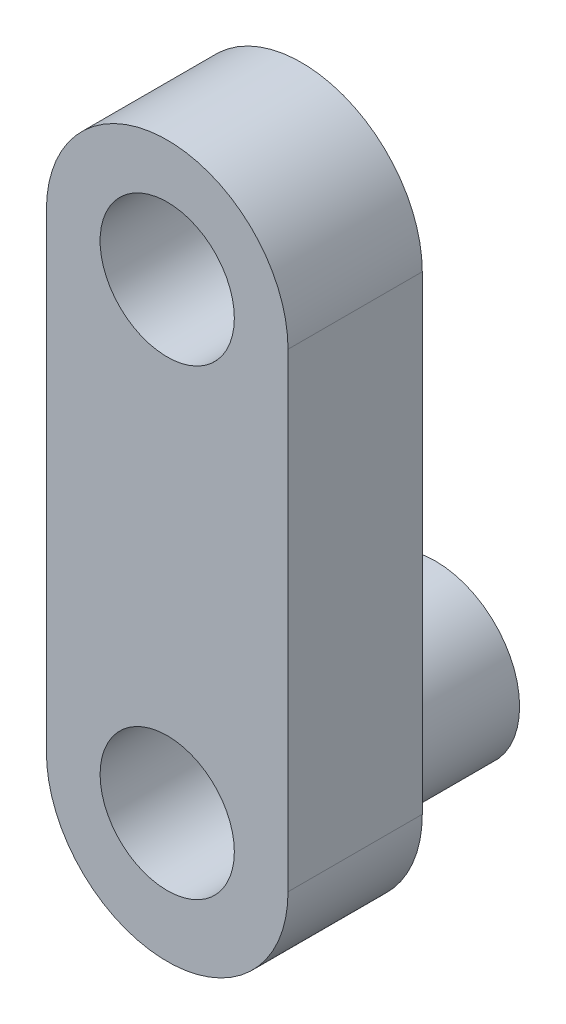
SolidWorks part; units mm, degrees
material "1023 Листовая углеродистая сталь (SS)"
ref_plane "Спереди" through (0, 0, 0) normal (0, 0, 1) x (1, 0, 0)
ref_plane "Сверху" through (0, 0, 0) normal (0, 1, 0) x (1, 0, 0)
ref_plane "Справа" through (0, 0, 0) normal (1, 0, 0) x (0, 0, -1)
sketch "Эскиз1" plane through (0, 0, 0) normal (0, 0, 1) x (1, 0, 0)
  line L0 (0, 70) -> (0, 0) construction
  line L1 (18, 70) -> (18, 0)
  line L2 (-18, 70) -> (-18, 0)
  circle A0 centre (0, 1.1538) radius 10
  circle A1 centre (0, 70) radius 10
  arc A2 (18, 70) -> (-18, 70) centre (0, 70) ccw
  arc A3 (-18, 0) -> (18, 0) centre (0, 0) ccw
  point P4 (0, 35)
  dimension "D2" = 20
  dimension "D3" = 36
  dimension "D1" = 70
extrude "Бобышка-Вытянуть1" add sketch "Эскиз1" along normal mid plane 20
sketch "Эскиз3" plane through (0, 0, -10) normal (0, 0, -1) x (-1, 0, 0)
  circle A0 centre (0, 1.1538) radius 10 construction
  circle A1 centre (0, 1.1538) radius 10
  circle A2 centre (0, 1.1538) radius 12.5
  dimension "D1" = 25
extrude "Бобышка-Вытянуть2" add sketch "Эскиз3" along normal blind 20
